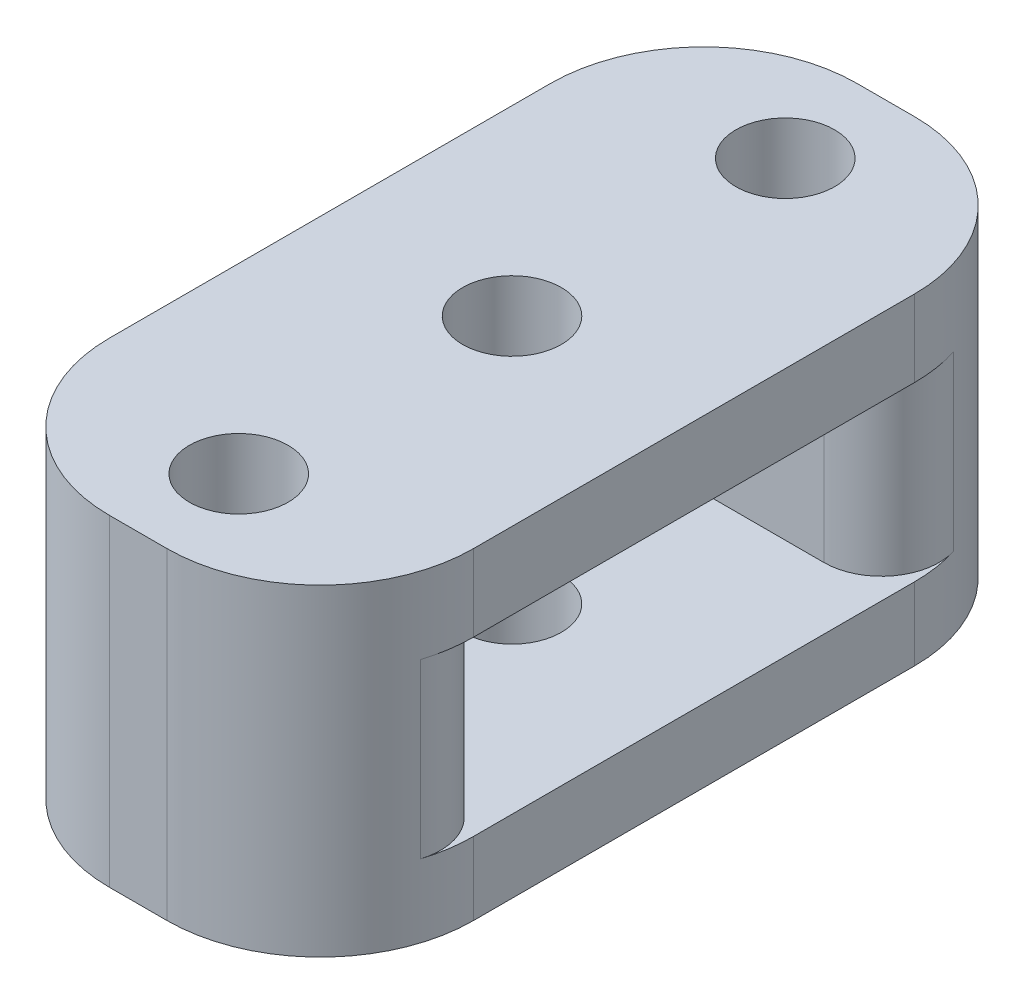
SolidWorks part; units mm, degrees
material "6063-T5"
ref_plane "Front Plane" through (0, 0, 0) normal (1, 0, 0) x (0, 1, 0)
ref_plane "Top Plane" through (0, 0, 0) normal (0, 0, 1) x (0, 1, 0)
ref_plane "Right Plane" through (0, 0, 0) normal (0, 1, 0) x (-1, 0, 0)
sketch "Sketch1" plane through (0, 0, 0) normal (0, 1, 0) x (-1, 0, 0)
  line L0 (-9.5, 9) -> (9.5, 9) construction
  line L1 (-9.5, -19.5) -> (9.5, -19.5)
  line L2 (-9.5, -19.5) -> (-9.5, 19.5)
  line L3 (-9.5, 19.5) -> (9.5, 19.5)
  line L4 (9.5, -19.5) -> (9.5, 19.5)
  line L5 (-9.5, -19.5) -> (9.5, 19.5) construction
  line L6 (-9.5, 19.5) -> (9.5, -19.5) construction
  line L7 (-9.5, -9) -> (9.5, -9) construction
  line L8 (0, 9) -> (0, 0) construction
  line L9 (0, 0) -> (0, -9) construction
  line L10 (0, 9) -> (0, 19.5) construction
  line L11 (0, -9) -> (0, -19.5) construction
  circle A0 centre (0, 0) radius 2.575
  circle A1 centre (0, 14.25) radius 2.575
  circle A2 centre (0, -14.25) radius 2.575
  point P0 (0, 0)
  dimension "D1" = 5.15
  dimension "D5" = 5.15
  dimension "D2" = 19
  dimension "D3" = 39
  dimension "D4" = 18
extrude "Boss-Extrude1" add sketch "Sketch1" along normal blind 3.8
sketch "Sketch2" plane through (0, 3.8, 0) normal (0, 1, 0) x (-1, 0, 0)
  line L0 (9.5, -19.5) -> (9.5, 19.5) construction
  line L1 (-9.5, 19.5) -> (9.5, 19.5)
  line L2 (-9.5, 19.5) -> (-9.5, 10)
  line L3 (-9.5, 10) -> (9.5, 10)
  line L4 (9.5, 19.5) -> (9.5, 10)
  line L5 (-9.5, 9) -> (9.5, 9) construction
  line L6 (-9.5, -19.5) -> (9.5, -19.5)
  line L7 (-9.5, -19.5) -> (-9.5, -10)
  line L8 (-9.5, -10) -> (9.5, -10)
  line L9 (9.5, -19.5) -> (9.5, -10)
  circle A0 centre (0, 14.25) radius 2.575
  circle A1 centre (0, -14.25) radius 2.575
  dimension "D1" = 1
extrude "Boss-Extrude2" add sketch "Sketch2" along normal blind 9
sketch "Sketch3" plane through (0, 12.8, 0) normal (0, 1, 0) x (-1, 0, 0)
  line L1 (-9.5, 19.5) -> (9.5, 19.5)
  line L2 (-9.5, 19.5) -> (-9.5, -19.5)
  line L3 (-9.5, -19.5) -> (9.5, -19.5)
  line L4 (9.5, 19.5) -> (9.5, -19.5)
  circle A0 centre (0, 14.25) radius 2.575
  circle A1 centre (0, 0) radius 2.575
  circle A2 centre (0, -14.25) radius 2.575
extrude "Boss-Extrude3" add sketch "Sketch3" along normal blind 4
fillet "Fillet1" radius 8 4 edges at (-9.5, 8.4, 19.5) (-9.5, 8.4, -19.5) (9.5, 8.4, -19.5) (9.5, 8.4, 19.5)
sketch "Sketch4" plane through (0, 16.8, 0) normal (0, 1, 0) x (-1, 0, 0)
  circle A0 centre (0, 14.25) radius 4.75 construction
  circle A1 centre (0, -14.25) radius 4.75 construction
  dimension "D1" = 9.5
fillet "Fillet2" radius 3 4 edges at (9.5, 8.3, -10) (-9.5, 8.3, -10) (-9.5, 8.3, 10) (9.5, 8.3, 10)
